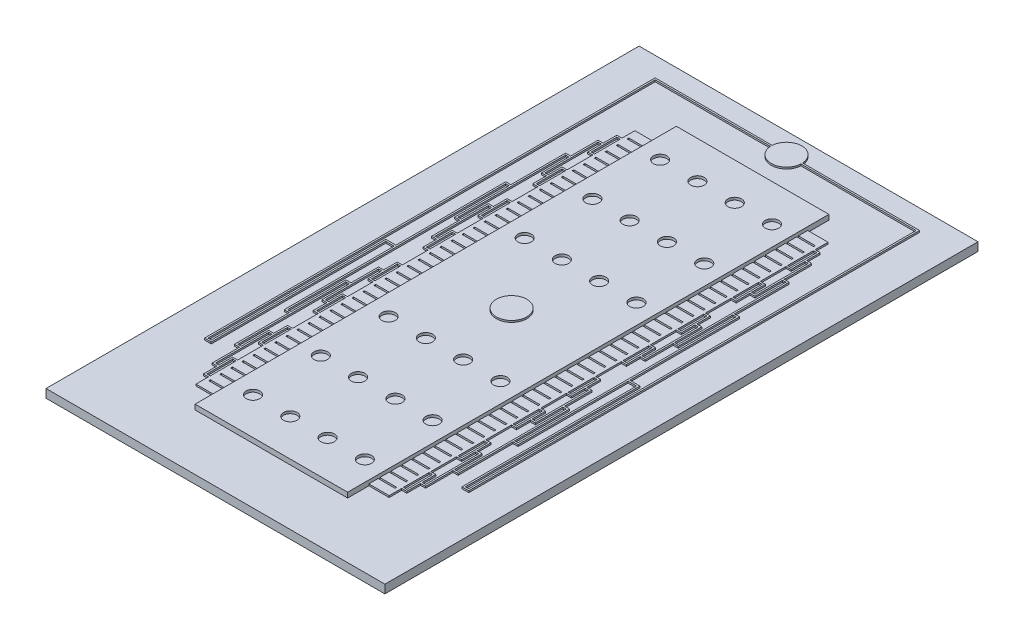
SolidWorks part; units mm, degrees
ref_plane "Front Plane" through (0, 0, 0) normal (0, 0, 1) x (1, 0, 0)
ref_plane "Top Plane" through (0, 0, 0) normal (0, 1, 0) x (1, 0, 0)
ref_plane "Right Plane" through (0, 0, 0) normal (1, 0, 0) x (0, 0, -1)
sketch "Sketch2" plane through (0, 0, 0) normal (0, 1, 0) x (1, 0, 0)
  line L1 (-10, 17.5) -> (10, 17.5)
  line L2 (-10, 17.5) -> (-10, -17.5)
  line L3 (-10, -17.5) -> (10, -17.5)
  line L4 (10, 17.5) -> (10, -17.5)
  line L5 (-10, 17.5) -> (10, -17.5) construction
  line L6 (-10, -17.5) -> (10, 17.5) construction
  point P0 (0, 0)
extrude "Boss-Extrude1" add sketch "Sketch2" along normal blind 0.5
sketch "Sketch3" plane through (0, 0.5, 0) normal (0, 1, 0) x (1, 0, 0)
  line L1 (-4.5, 14.2) -> (4.5, 14.2)
  line L2 (-4.5, 14.2) -> (-4.5, -14.2)
  line L3 (-4.5, -14.2) -> (4.5, -14.2)
  line L4 (4.5, 14.2) -> (4.5, -14.2)
  line L5 (-4.5, 14.2) -> (4.5, -14.2) construction
  line L6 (-4.5, -14.2) -> (4.5, 14.2) construction
  point P0 (0, 0)
extrude "Boss-Extrude2" add sketch "Sketch3" along normal blind 0.3
sketch "Sketch6" plane through (0, 0.5, 0) normal (0, 1, 0) x (1, 0, 0)
  line L0 (4.5, 12.95) -> (5.7, 12.95)
  line L1 (4.5, 12.95) -> (4.5, -12.95)
  line L2 (5.7, 12.95) -> (5.7, -12.95)
  line L3 (4.5, -12.95) -> (5.7, -12.95)
  line L4 (4.5, -14.2) -> (4.5, 14.2) construction
  line L5 (0, 23.9798) -> (0, -23.9798) construction
  line L6 (-5.7, 12.95) -> (-5.7, -12.95)
  line L7 (-4.5, -12.95) -> (-5.7, -12.95)
  line L8 (-4.5, 12.95) -> (-4.5, -12.95)
  line L9 (-4.5, 12.95) -> (-5.7, 12.95)
  point P0 (4.5, 14.1998)
  point P1 (4.5, 14.1998)
  point P6 (5.7, 0)
  point P10 (0, 0)
  point P14 (0, 0)
extrude "Boss-Extrude3" add sketch "Sketch6" along normal blind 0.1
sketch "Sketch8" plane through (0, 0.6, 0) normal (0, 1, 0) x (1, 0, 0)
  line L0 (4.5, 12.4) -> (5.5, 12.4)
  line L1 (4.5, 12.4) -> (4.5, 12.3)
  line L2 (5.5, 12.4) -> (5.5, 12.3)
  line L3 (4.5, 12.3) -> (5.5, 12.3)
  line L4 (-5.5, 12.4) -> (-4.5, 12.4)
  line L5 (-5.5, 12.4) -> (-5.5, 12.3)
  line L6 (-5.5, 12.3) -> (-4.5, 12.3)
  line L7 (-4.5, 12.4) -> (-4.5, 12.3)
  line L8 (-5.5, 11.75) -> (-4.5, 11.75)
  line L9 (-5.5, 11.75) -> (-5.5, 11.65)
  line L10 (-5.5, 11.65) -> (-4.5, 11.65)
  line L11 (-4.5, 11.75) -> (-4.5, 11.65)
  line L12 (-5.5, 11.1) -> (-4.5, 11.1)
  line L13 (-5.5, 11.1) -> (-5.5, 11)
  line L14 (-5.5, 11) -> (-4.5, 11)
  line L15 (-4.5, 11.1) -> (-4.5, 11)
  line L16 (-5.5, 10.45) -> (-4.5, 10.45)
  line L17 (-5.5, 10.45) -> (-5.5, 10.35)
  line L18 (-5.5, 10.35) -> (-4.5, 10.35)
  line L19 (-4.5, 10.45) -> (-4.5, 10.35)
  line L20 (-5.5, 9.8) -> (-4.5, 9.8)
  line L21 (-5.5, 9.8) -> (-5.5, 9.7)
  line L22 (-5.5, 9.7) -> (-4.5, 9.7)
  line L23 (-4.5, 9.8) -> (-4.5, 9.7)
  line L24 (-5.5, 9.15) -> (-4.5, 9.15)
  line L25 (-5.5, 9.15) -> (-5.5, 9.05)
  line L26 (-5.5, 9.05) -> (-4.5, 9.05)
  line L27 (-4.5, 9.15) -> (-4.5, 9.05)
  line L28 (-5.5, 8.5) -> (-4.5, 8.5)
  line L29 (-5.5, 8.5) -> (-5.5, 8.4)
  line L30 (-5.5, 8.4) -> (-4.5, 8.4)
  line L31 (-4.5, 8.5) -> (-4.5, 8.4)
  line L32 (-5.5, 7.85) -> (-4.5, 7.85)
  line L33 (-5.5, 7.85) -> (-5.5, 7.75)
  line L34 (-5.5, 7.75) -> (-4.5, 7.75)
  line L35 (-4.5, 7.85) -> (-4.5, 7.75)
  line L36 (-5.5, 7.2) -> (-4.5, 7.2)
  line L37 (-5.5, 7.2) -> (-5.5, 7.1)
  line L38 (-5.5, 7.1) -> (-4.5, 7.1)
  line L39 (-4.5, 7.2) -> (-4.5, 7.1)
  line L40 (-5.5, 6.55) -> (-4.5, 6.55)
  line L41 (-5.5, 6.55) -> (-5.5, 6.45)
  line L42 (-5.5, 6.45) -> (-4.5, 6.45)
  line L43 (-4.5, 6.55) -> (-4.5, 6.45)
  line L44 (-5.5, 5.9) -> (-4.5, 5.9)
  line L45 (-5.5, 5.9) -> (-5.5, 5.8)
  line L46 (-5.5, 5.8) -> (-4.5, 5.8)
  line L47 (-4.5, 5.9) -> (-4.5, 5.8)
  line L48 (-5.5, 5.25) -> (-4.5, 5.25)
  line L49 (-5.5, 5.25) -> (-5.5, 5.15)
  line L50 (-5.5, 5.15) -> (-4.5, 5.15)
  line L51 (-4.5, 5.25) -> (-4.5, 5.15)
  line L52 (-5.5, 4.6) -> (-4.5, 4.6)
  line L53 (-5.5, 4.6) -> (-5.5, 4.5)
  line L54 (-5.5, 4.5) -> (-4.5, 4.5)
  line L55 (-4.5, 4.6) -> (-4.5, 4.5)
  line L56 (-5.5, 3.95) -> (-4.5, 3.95)
  line L57 (-5.5, 3.95) -> (-5.5, 3.85)
  line L58 (-5.5, 3.85) -> (-4.5, 3.85)
  line L59 (-4.5, 3.95) -> (-4.5, 3.85)
  line L60 (-5.5, 3.3) -> (-4.5, 3.3)
  line L61 (-5.5, 3.3) -> (-5.5, 3.2)
  line L62 (-5.5, 3.2) -> (-4.5, 3.2)
  line L63 (-4.5, 3.3) -> (-4.5, 3.2)
  line L64 (-5.5, 2.65) -> (-4.5, 2.65)
  line L65 (-5.5, 2.65) -> (-5.5, 2.55)
  line L66 (-5.5, 2.55) -> (-4.5, 2.55)
  line L67 (-4.5, 2.65) -> (-4.5, 2.55)
  line L68 (-5.5, 2) -> (-4.5, 2)
  line L69 (-5.5, 2) -> (-5.5, 1.9)
  line L70 (-5.5, 1.9) -> (-4.5, 1.9)
  line L71 (-4.5, 2) -> (-4.5, 1.9)
  line L72 (-5.5, 1.35) -> (-4.5, 1.35)
  line L73 (-5.5, 1.35) -> (-5.5, 1.25)
  line L74 (-5.5, 1.25) -> (-4.5, 1.25)
  line L75 (-4.5, 1.35) -> (-4.5, 1.25)
  line L76 (-5.5, 0.7) -> (-4.5, 0.7)
  line L77 (-5.5, 0.7) -> (-5.5, 0.6)
  line L78 (-5.5, 0.6) -> (-4.5, 0.6)
  line L79 (-4.5, 0.7) -> (-4.5, 0.6)
  line L80 (-5.5, 0.05) -> (-4.5, 0.05)
  line L81 (-5.5, 0.05) -> (-5.5, -0.05)
  line L82 (-5.5, -0.05) -> (-4.5, -0.05)
  line L83 (-4.5, 0.05) -> (-4.5, -0.05)
  line L84 (-5.5, -0.6) -> (-4.5, -0.6)
  line L85 (-5.5, -0.6) -> (-5.5, -0.7)
  line L86 (-5.5, -0.7) -> (-4.5, -0.7)
  line L87 (-4.5, -0.6) -> (-4.5, -0.7)
  line L88 (-5.5, -1.25) -> (-4.5, -1.25)
  line L89 (-5.5, -1.25) -> (-5.5, -1.35)
  line L90 (-5.5, -1.35) -> (-4.5, -1.35)
  line L91 (-4.5, -1.25) -> (-4.5, -1.35)
  line L92 (-5.5, -1.9) -> (-4.5, -1.9)
  line L93 (-5.5, -1.9) -> (-5.5, -2)
  line L94 (-5.5, -2) -> (-4.5, -2)
  line L95 (-4.5, -1.9) -> (-4.5, -2)
  line L96 (-5.5, -2.55) -> (-4.5, -2.55)
  line L97 (-5.5, -2.55) -> (-5.5, -2.65)
  line L98 (-5.5, -2.65) -> (-4.5, -2.65)
  line L99 (-4.5, -2.55) -> (-4.5, -2.65)
  line L100 (-5.5, -3.2) -> (-4.5, -3.2)
  line L101 (-5.5, -3.2) -> (-5.5, -3.3)
  line L102 (-5.5, -3.3) -> (-4.5, -3.3)
  line L103 (-4.5, -3.2) -> (-4.5, -3.3)
  line L104 (-5.5, -3.85) -> (-4.5, -3.85)
  line L105 (-5.5, -3.85) -> (-5.5, -3.95)
  line L106 (-5.5, -3.95) -> (-4.5, -3.95)
  line L107 (-4.5, -3.85) -> (-4.5, -3.95)
  line L108 (-5.5, -4.5) -> (-4.5, -4.5)
  line L109 (-5.5, -4.5) -> (-5.5, -4.6)
  line L110 (-5.5, -4.6) -> (-4.5, -4.6)
  line L111 (-4.5, -4.5) -> (-4.5, -4.6)
  line L112 (-5.5, -5.15) -> (-4.5, -5.15)
  line L113 (-5.5, -5.15) -> (-5.5, -5.25)
  line L114 (-5.5, -5.25) -> (-4.5, -5.25)
  line L115 (-4.5, -5.15) -> (-4.5, -5.25)
  line L116 (-5.5, -5.8) -> (-4.5, -5.8)
  line L117 (-5.5, -5.8) -> (-5.5, -5.9)
  line L118 (-5.5, -5.9) -> (-4.5, -5.9)
  line L119 (-4.5, -5.8) -> (-4.5, -5.9)
  line L120 (-5.5, -6.45) -> (-4.5, -6.45)
  line L121 (-5.5, -6.45) -> (-5.5, -6.55)
  line L122 (-5.5, -6.55) -> (-4.5, -6.55)
  line L123 (-4.5, -6.45) -> (-4.5, -6.55)
  line L124 (-5.5, -7.1) -> (-4.5, -7.1)
  line L125 (-5.5, -7.1) -> (-5.5, -7.2)
  line L126 (-5.5, -7.2) -> (-4.5, -7.2)
  line L127 (-4.5, -7.1) -> (-4.5, -7.2)
  line L128 (-5.5, -7.75) -> (-4.5, -7.75)
  line L129 (-5.5, -7.75) -> (-5.5, -7.85)
  line L130 (-5.5, -7.85) -> (-4.5, -7.85)
  line L131 (-4.5, -7.75) -> (-4.5, -7.85)
  line L132 (-5.5, -8.4) -> (-4.5, -8.4)
  line L133 (-5.5, -8.4) -> (-5.5, -8.5)
  line L134 (-5.5, -8.5) -> (-4.5, -8.5)
  line L135 (-4.5, -8.4) -> (-4.5, -8.5)
  line L136 (-5.5, -9.05) -> (-4.5, -9.05)
  line L137 (-5.5, -9.05) -> (-5.5, -9.15)
  line L138 (-5.5, -9.15) -> (-4.5, -9.15)
  line L139 (-4.5, -9.05) -> (-4.5, -9.15)
  line L140 (-5.5, -9.7) -> (-4.5, -9.7)
  line L141 (-5.5, -9.7) -> (-5.5, -9.8)
  line L142 (-5.5, -9.8) -> (-4.5, -9.8)
  line L143 (-4.5, -9.7) -> (-4.5, -9.8)
  line L144 (-5.5, -10.35) -> (-4.5, -10.35)
  line L145 (-5.5, -10.35) -> (-5.5, -10.45)
  line L146 (-5.5, -10.45) -> (-4.5, -10.45)
  line L147 (-4.5, -10.35) -> (-4.5, -10.45)
  line L148 (-5.5, -11) -> (-4.5, -11)
  line L149 (-5.5, -11) -> (-5.5, -11.1)
  line L150 (-5.5, -11.1) -> (-4.5, -11.1)
  line L151 (-4.5, -11) -> (-4.5, -11.1)
  line L152 (-5.5, -11.65) -> (-4.5, -11.65)
  line L153 (-5.5, -11.65) -> (-5.5, -11.75)
  line L154 (-5.5, -11.75) -> (-4.5, -11.75)
  line L155 (-4.5, -11.65) -> (-4.5, -11.75)
  line L156 (-5.5, -12.3) -> (-4.5, -12.3)
  line L157 (-5.5, -12.3) -> (-5.5, -12.4)
  line L158 (-5.5, -12.4) -> (-4.5, -12.4)
  line L159 (-4.5, -12.3) -> (-4.5, -12.4)
  line L160 (4.5, 11.75) -> (5.5, 11.75)
  line L161 (4.5, 11.75) -> (4.5, 11.65)
  line L162 (4.5, 11.65) -> (5.5, 11.65)
  line L163 (5.5, 11.75) -> (5.5, 11.65)
  line L164 (4.5, 11.1) -> (5.5, 11.1)
  line L165 (4.5, 11.1) -> (4.5, 11)
  line L166 (4.5, 11) -> (5.5, 11)
  line L167 (5.5, 11.1) -> (5.5, 11)
  line L168 (4.5, 10.45) -> (5.5, 10.45)
  line L169 (4.5, 10.45) -> (4.5, 10.35)
  line L170 (4.5, 10.35) -> (5.5, 10.35)
  line L171 (5.5, 10.45) -> (5.5, 10.35)
  line L172 (4.5, 9.8) -> (5.5, 9.8)
  line L173 (4.5, 9.8) -> (4.5, 9.7)
  line L174 (4.5, 9.7) -> (5.5, 9.7)
  line L175 (5.5, 9.8) -> (5.5, 9.7)
  line L176 (4.5, 9.15) -> (5.5, 9.15)
  line L177 (4.5, 9.15) -> (4.5, 9.05)
  line L178 (4.5, 9.05) -> (5.5, 9.05)
  line L179 (5.5, 9.15) -> (5.5, 9.05)
  line L180 (4.5, 8.5) -> (5.5, 8.5)
  line L181 (4.5, 8.5) -> (4.5, 8.4)
  line L182 (4.5, 8.4) -> (5.5, 8.4)
  line L183 (5.5, 8.5) -> (5.5, 8.4)
  line L184 (4.5, 7.85) -> (5.5, 7.85)
  line L185 (4.5, 7.85) -> (4.5, 7.75)
  line L186 (4.5, 7.75) -> (5.5, 7.75)
  line L187 (5.5, 7.85) -> (5.5, 7.75)
  line L188 (4.5, 7.2) -> (5.5, 7.2)
  line L189 (4.5, 7.2) -> (4.5, 7.1)
  line L190 (4.5, 7.1) -> (5.5, 7.1)
  line L191 (5.5, 7.2) -> (5.5, 7.1)
  line L192 (4.5, 6.55) -> (5.5, 6.55)
  line L193 (4.5, 6.55) -> (4.5, 6.45)
  line L194 (4.5, 6.45) -> (5.5, 6.45)
  line L195 (5.5, 6.55) -> (5.5, 6.45)
  line L196 (4.5, 5.9) -> (5.5, 5.9)
  line L197 (4.5, 5.9) -> (4.5, 5.8)
  line L198 (4.5, 5.8) -> (5.5, 5.8)
  line L199 (5.5, 5.9) -> (5.5, 5.8)
  line L200 (4.5, 5.25) -> (5.5, 5.25)
  line L201 (4.5, 5.25) -> (4.5, 5.15)
  line L202 (4.5, 5.15) -> (5.5, 5.15)
  line L203 (5.5, 5.25) -> (5.5, 5.15)
  line L204 (4.5, 4.6) -> (5.5, 4.6)
  line L205 (4.5, 4.6) -> (4.5, 4.5)
  line L206 (4.5, 4.5) -> (5.5, 4.5)
  line L207 (5.5, 4.6) -> (5.5, 4.5)
  line L208 (4.5, 3.95) -> (5.5, 3.95)
  line L209 (4.5, 3.95) -> (4.5, 3.85)
  line L210 (4.5, 3.85) -> (5.5, 3.85)
  line L211 (5.5, 3.95) -> (5.5, 3.85)
  line L212 (4.5, 3.3) -> (5.5, 3.3)
  line L213 (4.5, 3.3) -> (4.5, 3.2)
  line L214 (4.5, 3.2) -> (5.5, 3.2)
  line L215 (5.5, 3.3) -> (5.5, 3.2)
  line L216 (4.5, 2.65) -> (5.5, 2.65)
  line L217 (4.5, 2.65) -> (4.5, 2.55)
  line L218 (4.5, 2.55) -> (5.5, 2.55)
  line L219 (5.5, 2.65) -> (5.5, 2.55)
  line L220 (4.5, 2) -> (5.5, 2)
  line L221 (4.5, 2) -> (4.5, 1.9)
  line L222 (4.5, 1.9) -> (5.5, 1.9)
  line L223 (5.5, 2) -> (5.5, 1.9)
  line L224 (4.5, 1.35) -> (5.5, 1.35)
  line L225 (4.5, 1.35) -> (4.5, 1.25)
  line L226 (4.5, 1.25) -> (5.5, 1.25)
  line L227 (5.5, 1.35) -> (5.5, 1.25)
  line L228 (4.5, 0.7) -> (5.5, 0.7)
  line L229 (4.5, 0.7) -> (4.5, 0.6)
  line L230 (4.5, 0.6) -> (5.5, 0.6)
  line L231 (5.5, 0.7) -> (5.5, 0.6)
  line L232 (4.5, 0.05) -> (5.5, 0.05)
  line L233 (4.5, 0.05) -> (4.5, -0.05)
  line L234 (4.5, -0.05) -> (5.5, -0.05)
  line L235 (5.5, 0.05) -> (5.5, -0.05)
  line L236 (4.5, -0.6) -> (5.5, -0.6)
  line L237 (4.5, -0.6) -> (4.5, -0.7)
  line L238 (4.5, -0.7) -> (5.5, -0.7)
  line L239 (5.5, -0.6) -> (5.5, -0.7)
  line L240 (4.5, -1.25) -> (5.5, -1.25)
  line L241 (4.5, -1.25) -> (4.5, -1.35)
  line L242 (4.5, -1.35) -> (5.5, -1.35)
  line L243 (5.5, -1.25) -> (5.5, -1.35)
  line L244 (4.5, -1.9) -> (5.5, -1.9)
  line L245 (4.5, -1.9) -> (4.5, -2)
  line L246 (4.5, -2) -> (5.5, -2)
  line L247 (5.5, -1.9) -> (5.5, -2)
  line L248 (4.5, -2.55) -> (5.5, -2.55)
  line L249 (4.5, -2.55) -> (4.5, -2.65)
  line L250 (4.5, -2.65) -> (5.5, -2.65)
  line L251 (5.5, -2.55) -> (5.5, -2.65)
  line L252 (4.5, -3.2) -> (5.5, -3.2)
  line L253 (4.5, -3.2) -> (4.5, -3.3)
  line L254 (4.5, -3.3) -> (5.5, -3.3)
  line L255 (5.5, -3.2) -> (5.5, -3.3)
  line L256 (4.5, -3.85) -> (5.5, -3.85)
  line L257 (4.5, -3.85) -> (4.5, -3.95)
  line L258 (4.5, -3.95) -> (5.5, -3.95)
  line L259 (5.5, -3.85) -> (5.5, -3.95)
  line L260 (4.5, -4.5) -> (5.5, -4.5)
  line L261 (4.5, -4.5) -> (4.5, -4.6)
  line L262 (4.5, -4.6) -> (5.5, -4.6)
  line L263 (5.5, -4.5) -> (5.5, -4.6)
  line L264 (4.5, -5.15) -> (5.5, -5.15)
  line L265 (4.5, -5.15) -> (4.5, -5.25)
  line L266 (4.5, -5.25) -> (5.5, -5.25)
  line L267 (5.5, -5.15) -> (5.5, -5.25)
  line L268 (4.5, -5.8) -> (5.5, -5.8)
  line L269 (4.5, -5.8) -> (4.5, -5.9)
  line L270 (4.5, -5.9) -> (5.5, -5.9)
  line L271 (5.5, -5.8) -> (5.5, -5.9)
  line L272 (4.5, -6.45) -> (5.5, -6.45)
  line L273 (4.5, -6.45) -> (4.5, -6.55)
  line L274 (4.5, -6.55) -> (5.5, -6.55)
  line L275 (5.5, -6.45) -> (5.5, -6.55)
  line L276 (4.5, -7.1) -> (5.5, -7.1)
  line L277 (4.5, -7.1) -> (4.5, -7.2)
  line L278 (4.5, -7.2) -> (5.5, -7.2)
  line L279 (5.5, -7.1) -> (5.5, -7.2)
  line L280 (4.5, -7.75) -> (5.5, -7.75)
  line L281 (4.5, -7.75) -> (4.5, -7.85)
  line L282 (4.5, -7.85) -> (5.5, -7.85)
  line L283 (5.5, -7.75) -> (5.5, -7.85)
  line L284 (4.5, -8.4) -> (5.5, -8.4)
  line L285 (4.5, -8.4) -> (4.5, -8.5)
  line L286 (4.5, -8.5) -> (5.5, -8.5)
  line L287 (5.5, -8.4) -> (5.5, -8.5)
  line L288 (4.5, -9.05) -> (5.5, -9.05)
  line L289 (4.5, -9.05) -> (4.5, -9.15)
  line L290 (4.5, -9.15) -> (5.5, -9.15)
  line L291 (5.5, -9.05) -> (5.5, -9.15)
  line L292 (4.5, -9.7) -> (5.5, -9.7)
  line L293 (4.5, -9.7) -> (4.5, -9.8)
  line L294 (4.5, -9.8) -> (5.5, -9.8)
  line L295 (5.5, -9.7) -> (5.5, -9.8)
  line L296 (4.5, -10.35) -> (5.5, -10.35)
  line L297 (4.5, -10.35) -> (4.5, -10.45)
  line L298 (4.5, -10.45) -> (5.5, -10.45)
  line L299 (5.5, -10.35) -> (5.5, -10.45)
  line L300 (4.5, -11) -> (5.5, -11)
  line L301 (4.5, -11) -> (4.5, -11.1)
  line L302 (4.5, -11.1) -> (5.5, -11.1)
  line L303 (5.5, -11) -> (5.5, -11.1)
  line L304 (4.5, -11.65) -> (5.5, -11.65)
  line L305 (4.5, -11.65) -> (4.5, -11.75)
  line L306 (4.5, -11.75) -> (5.5, -11.75)
  line L307 (5.5, -11.65) -> (5.5, -11.75)
  line L308 (4.5, -12.3) -> (5.5, -12.3)
  line L309 (4.5, -12.3) -> (4.5, -12.4)
  line L310 (4.5, -12.4) -> (5.5, -12.4)
  line L311 (5.5, -12.3) -> (5.5, -12.4)
  point P0 (4.5, 12.4)
  dimension "D1" = 0.55
  dimension "D2" = 2
  dimension "D3" = 39
extrude "Cut-Extrude1" cut sketch "Sketch8" against normal blind 0.1 contours L0 L1 L3 L2 | L162 L163 L160 L161 | L166 L167 L164 L165 | L170 L171 L168 L169 | L174 L175 L172 L173 | L176 L179 L178 L177 | L182 L183 L180 L181 | L184 L187 L186 L185 | L188 L191 L190 L189 | L192 L195 L194 L193 | L196 L199 L198 L197 | L200 L203 L202 L201 | L204 L207 L206 L205 | L208 L211 L210 L209 | L212 L215 L214 L213 | L216 L219 L218 L217 | L220 L223 L222 L221 | L224 L227 L226 L225 | L228 L231 L230 L229 | L232 L235 L234 L233 | L236 L239 L238 L237 | L240 L243 L242 L241 | L244 L247 L246 L245 | L248 L251 L250 L249 | L254 L255 L252 L253 | L256 L259 L258 L257 | L260 L263 L262 L261 | L266 L267 L264 L265 | L268 L271 L270 L269 | L272 L275 L274 L273 | L276 L279 L278 L277 | L280 L283 L282 L281 | L284 L287 L286 L285 | L288 L291 L290 L289 | L292 L295 L294 L293 | L296 L299 L298 L297 | L300 L303 L302 L301 | L304 L307 L306 L305 | L308 L311 L310 L309 | L156 L159 L158 L157 | L152 L155 L154 L153 | L150 L151 L148 L149 | L144 L147 L146 L145 | L140 L143 L142 L141 | L136 L139 L138 L137 | L134 L135 L132 L133 | L128 L131 L130 L129 | L124 L127 L126 L125 | L120 L123 L122 L121 | L116 L119 L118 L117 | L112 L115 L114 L113 | L108 L111 L110 L109 | L104 L107 L106 L105 | L100 L103 L102 L101 | L98 L99 L96 L97 | L94 L95 L92 L93 | L4 L7 L6 L5 | L8 L11 L10 L9 | L12 L15 L14 L13 | L16 L19 L18 L17 | L20 L23 L22 L21 | L24 L27 L26 L25 | L28 L31 L30 L29 | L32 L35 L34 L33 | L36 L39 L38 L37 | L40 L43 L42 L41 | L44 L47 L46 L45 | L48 L51 L50 L49 | L52 L55 L54 L53 | L56 L59 L58 L57 | L88 L91 L90 L89 | L84 L87 L86 L85 | L82 L83 L80 L81 | L78 L79 L76 L77 | L72 L75 L74 L73 | L68 L71 L70 L69 | L64 L67 L66 L65 | L60 L63 L62 L61
sketch "Sketch9" plane through (0, 0.5, 0) normal (0, 1, 0) x (1, 0, 0)
  line L0 (0, 23.039) -> (0, -23.039) construction
  line L1 (-7.8, 16.25) -> (7.8, 16.25)
  line L2 (4.5, 14.2) -> (-4.5, 14.2) construction
  line L3 (-7.7, 16.15) -> (7.7, 16.15)
  line L4 (-7.8, 16.25) -> (-7.8, -10.35)
  line L5 (-7.7, 16.15) -> (-7.7, -10.25)
  line L6 (-7.8, -10.35) -> (-7.4, -10.35)
  line L7 (-7.7, -10.25) -> (-7.5, -10.25)
  line L8 (8.7438, 0) -> (-8.7438, 0) construction
  line L9 (-7.5, -10.25) -> (-7.5, 0.05)
  line L10 (-7.4, -10.35) -> (-7.4, -0.05)
  line L11 (-5.7, 12.95) -> (-5.7, -12.95) construction
  line L12 (-7.5, 0.05) -> (-6.9, 0.05)
  line L13 (-7.4, -0.05) -> (-6.9, -0.05)
  line L14 (-5.7, 12.19) -> (-6, 12.19)
  line L15 (-5.7, 12.09) -> (-5.9, 12.09)
  line L16 (-5.7, 10.57) -> (-5.9, 10.57)
  line L17 (-5.7, 10.47) -> (-6, 10.47)
  line L18 (-5.9, 12.09) -> (-5.9, 10.57)
  line L19 (-6, 12.19) -> (-6, 11.38)
  line L20 (-6, 10.47) -> (-6, 11.28)
  line L21 (-6, 8.95) -> (-6, 8.14)
  line L22 (-5.9, 8.85) -> (-5.9, 7.33)
  line L23 (-6, 7.23) -> (-6, 8.04)
  line L24 (-5.7, 7.33) -> (-5.9, 7.33)
  line L25 (-5.7, 7.23) -> (-6, 7.23)
  line L26 (-5.7, 8.95) -> (-6, 8.95)
  line L27 (-5.7, 8.85) -> (-5.9, 8.85)
  line L28 (-6, 5.71) -> (-6, 4.9)
  line L29 (-5.9, 5.61) -> (-5.9, 4.09)
  line L30 (-6, 3.99) -> (-6, 4.8)
  line L31 (-5.7, 4.09) -> (-5.9, 4.09)
  line L32 (-5.7, 3.99) -> (-6, 3.99)
  line L33 (-5.7, 5.71) -> (-6, 5.71)
  line L34 (-5.7, 5.61) -> (-5.9, 5.61)
  line L35 (-6, 2.47) -> (-6, 1.66)
  line L36 (-5.9, 2.37) -> (-5.9, 0.85)
  line L37 (-6, 0.75) -> (-6, 1.56)
  line L38 (-5.7, 0.85) -> (-5.9, 0.85)
  line L39 (-5.7, 0.75) -> (-6, 0.75)
  line L40 (-5.7, 2.47) -> (-6, 2.47)
  line L41 (-5.7, 2.37) -> (-5.9, 2.37)
  line L42 (-6, -0.77) -> (-6, -1.58)
  line L43 (-5.9, -0.87) -> (-5.9, -2.39)
  line L44 (-6, -2.49) -> (-6, -1.68)
  line L45 (-5.7, -2.39) -> (-5.9, -2.39)
  line L46 (-5.7, -2.49) -> (-6, -2.49)
  line L47 (-5.7, -0.77) -> (-6, -0.77)
  line L48 (-5.7, -0.87) -> (-5.9, -0.87)
  line L49 (-6, -4.01) -> (-6, -4.82)
  line L50 (-5.9, -4.11) -> (-5.9, -5.63)
  line L51 (-6, -5.73) -> (-6, -4.92)
  line L52 (-5.7, -5.63) -> (-5.9, -5.63)
  line L53 (-5.7, -5.73) -> (-6, -5.73)
  line L54 (-5.7, -4.01) -> (-6, -4.01)
  line L55 (-5.7, -4.11) -> (-5.9, -4.11)
  line L56 (-6, -7.25) -> (-6, -8.06)
  line L57 (-5.9, -7.35) -> (-5.9, -8.87)
  line L58 (-6, -8.97) -> (-6, -8.16)
  line L59 (-5.7, -8.87) -> (-5.9, -8.87)
  line L60 (-5.7, -8.97) -> (-6, -8.97)
  line L61 (-5.7, -7.25) -> (-6, -7.25)
  line L62 (-5.7, -7.35) -> (-5.9, -7.35)
  line L63 (-6, -10.49) -> (-6, -11.3)
  line L64 (-5.9, -10.59) -> (-5.9, -12.11)
  line L65 (-6, -12.21) -> (-6, -11.4)
  line L66 (-5.7, -12.11) -> (-5.9, -12.11)
  line L67 (-5.7, -12.21) -> (-6, -12.21)
  line L68 (-5.7, -10.49) -> (-6, -10.49)
  line L69 (-5.7, -10.59) -> (-5.9, -10.59)
  line L70 (-6, 11.38) -> (-6.3, 11.38)
  line L71 (-6, 11.28) -> (-6.2, 11.28)
  line L72 (-6, 8.14) -> (-6.2, 8.14)
  line L73 (-6, 8.04) -> (-6.3, 8.04)
  line L74 (-6, 4.9) -> (-6.3, 4.9)
  line L75 (-6, 4.8) -> (-6.2, 4.8)
  line L76 (-6, 1.56) -> (-6.3, 1.56)
  line L77 (-6, 1.66) -> (-6.2, 1.66)
  line L78 (-6, -1.58) -> (-6.3, -1.58)
  line L79 (-6, -1.68) -> (-6.2, -1.68)
  line L80 (-6, -4.92) -> (-6.3, -4.92)
  line L81 (-6, -4.82) -> (-6.2, -4.82)
  line L82 (-6, -8.06) -> (-6.3, -8.06)
  line L83 (-6, -8.16) -> (-6.2, -8.16)
  line L84 (-6, -11.4) -> (-6.3, -11.4)
  line L85 (-6, -11.3) -> (-6.2, -11.3)
  line L86 (-6.2, -8.16) -> (-6.2, -11.3)
  line L87 (-6.2, -1.68) -> (-6.2, -4.82)
  line L88 (-6.2, 4.8) -> (-6.2, 1.66)
  line L89 (-6.2, 11.28) -> (-6.2, 8.14)
  line L90 (-6.3, 11.38) -> (-6.3, 9.76)
  line L91 (-6.3, 8.04) -> (-6.3, 9.66)
  line L92 (-6.3, 4.9) -> (-6.3, 3.2981)
  line L93 (-6.3, 1.56) -> (-6.3, 3.2104)
  line L94 (-6.3, -1.58) -> (-6.3, -3.2)
  line L95 (-6.3, -4.92) -> (-6.3, -3.3)
  line L96 (-6.3, -8.06) -> (-6.3, -9.68)
  line L97 (-6.3, -11.4) -> (-6.3, -9.78)
  line L98 (-6.3, -9.78) -> (-6.6, -9.78)
  line L99 (-6.3, -9.68) -> (-6.5, -9.68)
  line L100 (-6.3, -3.2) -> (-6.6, -3.2)
  line L101 (-6.3, -3.3) -> (-6.5, -3.3)
  line L102 (-6.3, 3.2104) -> (-6.6, 3.2104)
  line L103 (-6.3, 3.2981) -> (-6.5, 3.2981)
  line L104 (-6.3, 9.76) -> (-6.6, 9.76)
  line L105 (-6.3, 9.66) -> (-6.5, 9.66)
  line L106 (-6.5, -9.68) -> (-6.5, -3.3)
  line L107 (-6.5, 3.2981) -> (-6.5, 9.66)
  line L108 (-6.6, 9.76) -> (-6.6, 6.529)
  line L109 (-6.6, 3.2104) -> (-6.6, 6.429)
  line L110 (-6.6, -3.2) -> (-6.6, -6.44)
  line L111 (-6.6, -9.78) -> (-6.6, -6.54)
  line L112 (-6.6, -6.54) -> (-6.9, -6.54)
  line L113 (-6.6, -6.44) -> (-6.8, -6.44)
  line L114 (-6.6, 6.529) -> (-6.9, 6.529)
  line L115 (-6.6, 6.429) -> (-6.8, 6.429)
  line L116 (-6.9, -6.54) -> (-6.9, -0.05)
  line L117 (-6.9, 6.529) -> (-6.9, 0.05)
  line L118 (-6.8, -6.44) -> (-6.8, 6.429)
  line L119 (5.7, -12.21) -> (6, -12.21)
  line L120 (5.7, -12.11) -> (5.9, -12.11)
  line L121 (6, -12.21) -> (6, -11.4)
  line L122 (6, -11.4) -> (6.3, -11.4)
  line L123 (6, -11.3) -> (6.2, -11.3)
  line L124 (5.9, -10.59) -> (5.9, -12.11)
  line L125 (6, -10.49) -> (6, -11.3)
  line L126 (5.7, -10.59) -> (5.9, -10.59)
  line L127 (5.7, -10.49) -> (6, -10.49)
  line L128 (6.3, -9.68) -> (6.5, -9.68)
  line L129 (6.3, -11.4) -> (6.3, -9.78)
  line L130 (6.3, -9.78) -> (6.6, -9.78)
  line L131 (7.8, -10.35) -> (7.4, -10.35)
  line L132 (7.7, -10.25) -> (7.5, -10.25)
  line L133 (5.7, -8.97) -> (6, -8.97)
  line L134 (5.7, -8.87) -> (5.9, -8.87)
  line L135 (6, -8.97) -> (6, -8.16)
  line L136 (6.3, -8.06) -> (6.3, -9.68)
  line L137 (6.2, -8.16) -> (6.2, -11.3)
  line L138 (6, -8.16) -> (6.2, -8.16)
  line L139 (6, -8.06) -> (6.3, -8.06)
  line L140 (5.9, -7.35) -> (5.9, -8.87)
  line L141 (6, -7.25) -> (6, -8.06)
  line L142 (5.7, -7.35) -> (5.9, -7.35)
  line L143 (5.7, -7.25) -> (6, -7.25)
  line L144 (6.6, -9.78) -> (6.6, -6.54)
  line L145 (6.6, -6.54) -> (6.9, -6.54)
  line L146 (6.6, -6.44) -> (6.8, -6.44)
  line L147 (5.7, -5.73) -> (6, -5.73)
  line L148 (5.7, -5.63) -> (5.9, -5.63)
  line L149 (6, -5.73) -> (6, -4.92)
  line L150 (5.9, -4.11) -> (5.9, -5.63)
  line L151 (5.7, -4.01) -> (6, -4.01)
  line L152 (5.7, -4.11) -> (5.9, -4.11)
  line L153 (6, -4.01) -> (6, -4.82)
  line L154 (6, -4.92) -> (6.3, -4.92)
  line L155 (6, -4.82) -> (6.2, -4.82)
  line L156 (6.3, -4.92) -> (6.3, -3.3)
  line L157 (6.6, -3.2) -> (6.6, -6.44)
  line L158 (6.5, -9.68) -> (6.5, -3.3)
  line L159 (6.3, -3.3) -> (6.5, -3.3)
  line L160 (6.3, -3.2) -> (6.6, -3.2)
  line L161 (5.7, -2.49) -> (6, -2.49)
  line L162 (5.7, -2.39) -> (5.9, -2.39)
  line L163 (6, -2.49) -> (6, -1.68)
  line L164 (6.3, -1.58) -> (6.3, -3.2)
  line L165 (6.2, -1.68) -> (6.2, -4.82)
  line L166 (6, -1.68) -> (6.2, -1.68)
  line L167 (6, -1.58) -> (6.3, -1.58)
  line L168 (5.9, -0.87) -> (5.9, -2.39)
  line L169 (6, -0.77) -> (6, -1.58)
  line L170 (5.7, -0.87) -> (5.9, -0.87)
  line L171 (5.7, -0.77) -> (6, -0.77)
  line L172 (6.9, -6.54) -> (6.9, -0.05)
  line L173 (7.5, -10.25) -> (7.5, 0.05)
  line L174 (7.4, -10.35) -> (7.4, -0.05)
  line L175 (7.4, -0.05) -> (6.9, -0.05)
  line L176 (7.5, 0.05) -> (6.9, 0.05)
  line L177 (5.7, 0.75) -> (6, 0.75)
  line L178 (5.7, 0.85) -> (5.9, 0.85)
  line L179 (6, 0.75) -> (6, 1.56)
  line L180 (6, 1.56) -> (6.3, 1.56)
  line L181 (6, 1.66) -> (6.2, 1.66)
  line L182 (5.9, 2.37) -> (5.9, 0.85)
  line L183 (6, 2.47) -> (6, 1.66)
  line L184 (5.7, 2.37) -> (5.9, 2.37)
  line L185 (5.7, 2.47) -> (6, 2.47)
  line L186 (6.3, 3.2104) -> (6.6, 3.2104)
  line L187 (6.3, 1.56) -> (6.3, 3.2104)
  line L188 (6.3, 3.2981) -> (6.5, 3.2981)
  line L189 (5.7, 3.99) -> (6, 3.99)
  line L190 (5.7, 4.09) -> (5.9, 4.09)
  line L191 (6.3, 4.9) -> (6.3, 3.2981)
  line L192 (6.2, 4.8) -> (6.2, 1.66)
  line L193 (6, 3.99) -> (6, 4.8)
  line L194 (6, 4.8) -> (6.2, 4.8)
  line L195 (6, 4.9) -> (6.3, 4.9)
  line L196 (6, 5.71) -> (6, 4.9)
  line L197 (5.9, 5.61) -> (5.9, 4.09)
  line L198 (5.7, 5.61) -> (5.9, 5.61)
  line L199 (5.7, 5.71) -> (6, 5.71)
  line L200 (6.6, 3.2104) -> (6.6, 6.429)
  line L201 (6.9, 6.529) -> (6.9, 0.05)
  line L202 (6.8, -6.44) -> (6.8, 6.429)
  line L203 (6.6, 6.429) -> (6.8, 6.429)
  line L204 (6.6, 6.529) -> (6.9, 6.529)
  line L205 (5.7, 7.23) -> (6, 7.23)
  line L206 (5.7, 7.33) -> (5.9, 7.33)
  line L207 (6, 7.23) -> (6, 8.04)
  line L208 (6, 8.04) -> (6.3, 8.04)
  line L209 (6, 8.14) -> (6.2, 8.14)
  line L210 (5.9, 8.85) -> (5.9, 7.33)
  line L211 (6, 8.95) -> (6, 8.14)
  line L212 (5.7, 8.85) -> (5.9, 8.85)
  line L213 (5.7, 8.95) -> (6, 8.95)
  line L214 (6.3, 8.04) -> (6.3, 9.66)
  line L215 (6.6, 9.76) -> (6.6, 6.529)
  line L216 (6.5, 3.2981) -> (6.5, 9.66)
  line L217 (6.3, 9.66) -> (6.5, 9.66)
  line L218 (6.3, 9.76) -> (6.6, 9.76)
  line L219 (6.2, 11.28) -> (6.2, 8.14)
  line L220 (6.3, 11.38) -> (6.3, 9.76)
  line L221 (5.7, 10.47) -> (6, 10.47)
  line L222 (5.7, 10.57) -> (5.9, 10.57)
  line L223 (6, 10.47) -> (6, 11.28)
  line L224 (6, 11.28) -> (6.2, 11.28)
  line L225 (6, 11.38) -> (6.3, 11.38)
  line L226 (5.9, 12.09) -> (5.9, 10.57)
  line L227 (6, 12.19) -> (6, 11.38)
  line L228 (5.7, 12.09) -> (5.9, 12.09)
  line L229 (5.7, 12.19) -> (6, 12.19)
  line L230 (7.7, 16.15) -> (7.7, -10.25)
  line L231 (7.8, 16.25) -> (7.8, -10.35)
  circle A0 centre (0, 16.2) radius 0.9
  point P0 (0, 0)
  point P1 (0, 16.15)
  point P5 (0, 0)
  point P6 (0, 16.2)
  point P9 (0, 14.2)
  point P12 (0, 16.25)
  point P18 (0, 16.25)
  point P20 (0, 16.15)
  point P22 (-7.5, 0)
  point P26 (0, 0)
  point P30 (-5.7, 0)
  point P33 (-5.7, 12.19)
  point P34 (-5.7, 12.95)
  point P38 (-5.7, 12.14)
  point P39 (-5.7, 11.33)
  point P40 (-5.7, 10.52)
  point P41 (-5.7, 9.71)
  point P42 (-5.7, 8.9)
  point P43 (-5.7, 8.09)
  point P44 (-5.7, 7.28)
  point P45 (-5.7, 6.47)
  point P46 (-5.7, 5.66)
  point P47 (-5.7, 4.85)
  point P48 (-5.7, 4.04)
  point P49 (-5.7, 3.23)
  point P50 (-5.7, 2.42)
  point P51 (-5.7, 1.61)
  point P52 (-5.7, 0.8)
  point P53 (-5.7, -0.01)
  point P54 (-5.7, -0.82)
  point P55 (-5.7, -1.63)
  point P56 (-5.7, -2.44)
  point P57 (-5.7, -3.25)
  point P58 (-5.7, -4.06)
  point P59 (-5.7, -4.87)
  point P60 (-5.7, -5.68)
  point P61 (-5.7, -6.49)
  point P62 (-5.7, -7.3)
  point P63 (-5.7, -8.11)
  point P64 (-5.7, -8.92)
  point P65 (-5.7, -9.73)
  point P66 (-5.7, -10.54)
  point P67 (-5.7, -11.35)
  point P68 (-5.7, -12.16)
  point P69 (-5.7, -12.97)
  point P70 (-5.7, 12.09)
  point P71 (-5.7, 10.47)
  point P72 (-5.7, 10.57)
  point P73 (-5.7, 8.95)
  point P74 (-5.7, 8.85)
  point P75 (-5.7, 7.33)
  point P76 (-5.7, 7.23)
  point P77 (-5.7, 5.71)
  point P78 (-5.7, 5.61)
  point P79 (-5.7, 4.09)
  point P80 (-5.7, 3.99)
  point P81 (-5.7, 2.47)
  point P82 (-5.7, 2.37)
  point P83 (-5.7, 0.85)
  point P84 (-5.7, 0.75)
  point P87 (-5.9, 11.28)
  point P94 (-5.9, 11.33)
  point P96 (-5.9, 11.38)
  point P179 (-6.2, 3.18)
  point P180 (-6.2, 9.76)
  point P182 (-6.2, 9.66)
  point P183 (-6.2, -3.2)
  point P184 (-6.2, -3.3)
  point P186 (-6.2, -9.68)
  point P187 (-6.2, -9.78)
  point P188 (-6.2, 3.28)
  point P192 (-6.2, 3.23)
  point P198 (-6.2, 9.71)
  point P203 (-6.2, -3.25)
  point P206 (-6.2, -9.73)
  point P208 (-6.5, -6.54)
  point P211 (-6.5, -6.44)
  point P212 (-6.5, 6.529)
  point P214 (-6.5, 6.429)
  point P220 (-6.5, -6.49)
  point P221 (-6.5, 6.479)
  line M13 (-5.7, -12.95) -> (-5.7, 12.95)
  line M19 (5.7, 12.95) -> (5.7, -12.95)
  dimension "D2" = 0.05
  dimension "D1" = 2
  dimension "D3" = 0.05
  dimension "D4" = 0.05
  dimension "D5" = 0.05
  dimension "D6" = 33
  dimension "D7" = 0.05
  dimension "D8" = 0.05
  dimension "D9" = 0.05
  dimension "D10" = 0.05
  dimension "D11" = 0.05
  dimension "D12" = 0.05
  dimension "D13" = 0.05
  dimension "D14" = 0.05
  dimension "D15" = 0.05
  dimension "D16" = 0.05
  dimension "D17" = 0.05
  dimension "D18" = 0.05
  dimension "D19" = 0.05
  dimension "D20" = 0.05
  dimension "D21" = 0.05
  dimension "D22" = 0.05
  dimension "D23" = 0.05
  dimension "D24" = 0.05
  dimension "D25" = 8
  dimension "D26" = 0.05
  dimension "D27" = 0.05
  dimension "D28" = 0.05
  dimension "D29" = 0.05
  dimension "D30" = 0.05
  dimension "D31" = 0.05
  dimension "D32" = 0.05
  dimension "D33" = 0.05
  dimension "D34" = 0.05
  dimension "D35" = 0.05
  dimension "D36" = 0.05
  dimension "D37" = 0.05
  dimension "D38" = 0.1
  dimension "D39" = 0.2
  dimension "D40" = 0.3
  dimension "D41" = 0.1
  dimension "D42" = 0.3
  dimension "D43" = 0.2
  dimension "D44" = 0.2
  dimension "D45" = 0.3
  dimension "D46" = 0.2
  dimension "D47" = 0.3
  dimension "D48" = 0.1
  dimension "D49" = 0.2
  dimension "D50" = 0.3
  dimension "D51" = 0.1
  dimension "D52" = 0.1
  dimension "D53" = 0.1
  dimension "D54" = 0.1
  dimension "D55" = 0.3
  dimension "D56" = 0.2
  dimension "D57" = 0.3
  dimension "0.1" = 0.1
  dimension "D58" = 0.2
  dimension "D59" = 0.1
  dimension "D60" = 0.2
  dimension "0.3" = 0.3
  dimension "D61" = 0.1
  dimension "D62" = 0.2
  dimension "D63" = 0.3
  dimension "D64" = 0.3
  dimension "D65" = 0.2
  dimension "D66" = 0.1
  dimension "D67" = 0.5
extrude "Boss-Extrude4" add sketch "Sketch9" along normal blind 0.1 contours A0 L1 L4 L6 L10 L13 L116 L112 L111 L98 L97 L84 L65 L67 L66 L64 L69 L68 L63 L85 L86 L83 L58 L60 L59 L57 L62 L61 L56 L82 L96 L99 L106 L101 L95 L80 L51 L53 L52 L50 L55 L54 L49 L81 L87 M13 | A0 L3 L230 L132 L173 L176 L201 L204 L215 L218 L220 L225 L227 L229 L228 L226 L222 L221 L223 L224 L219 L209 L211 L213 L212 L210 L206 L205 L207 L208 L214 L217 L216 L188 L191 L195 L196 L199 L198 L197 L190 L189 L193 L194 L192 M19 | L3 A0 L1 | L1 A0 | L3 A0 region at (-4.3493, 0.5, -16.2207) region at (0, 0.5, -16.6091) region at (0, 0.5, -16.2) region at (4.3493, 0.5, -16.2207) region at (0, 0.5, -15.7909)
sketch "Sketch10" plane through (0, 0.8, 0) normal (0, 1, 0) x (1, 0, 0)
  line L0 (-4.2645, 0) -> (4.2645, 0) construction
  line L1 (0, -14.0113) -> (0, 14.0113) construction
  circle A1 centre (0.025, -0.0492) radius 0.9
  point P3 (0, 0)
  point P6 (0, 0)
extrude "Boss-Extrude5" add sketch "Sketch10" along normal blind 0.1 contours A1
sketch "Sketch11" plane through (0, 0.8, 0) normal (0, 1, 0) x (1, 0, 0)
  line L1 (-4.1511, 0) -> (4.1511, 0) construction
  line L2 (0, -13.9488) -> (0, 13.9488) construction
  circle A0 centre (-3.2696, 12.0132) radius 0.4
  circle A1 centre (-1.0696, 12.0132) radius 0.4
  circle A2 centre (1.1304, 12.0132) radius 0.4
  circle A3 centre (3.3304, 12.0132) radius 0.4
  circle A4 centre (-1.0696, 8.0132) radius 0.4
  circle A5 centre (1.1304, 8.0132) radius 0.4
  circle A6 centre (3.3304, 8.0132) radius 0.4
  circle A7 centre (-1.0696, 4.0132) radius 0.4
  circle A8 centre (1.1304, 4.0132) radius 0.4
  circle A9 centre (3.3304, 4.0132) radius 0.4
  circle A10 centre (-3.2696, 8.0132) radius 0.4
  circle A11 centre (-3.2696, 4.0132) radius 0.4
  circle A12 centre (3.3304, -4.0132) radius 0.4
  circle A13 centre (1.1304, -4.0132) radius 0.4
  circle A14 centre (-1.0696, -4.0132) radius 0.4
  circle A15 centre (-3.2696, -4.0132) radius 0.4
  circle A16 centre (3.3304, -8.0132) radius 0.4
  circle A17 centre (1.1304, -8.0132) radius 0.4
  circle A18 centre (-1.0696, -8.0132) radius 0.4
  circle A19 centre (-3.2696, -8.0132) radius 0.4
  circle A20 centre (3.3304, -12.0132) radius 0.4
  circle A21 centre (1.1304, -12.0132) radius 0.4
  circle A22 centre (-1.0696, -12.0132) radius 0.4
  circle A23 centre (-3.2696, -12.0132) radius 0.4
  point P5 (0, 0)
  point P8 (0, 0)
  dimension "D1" = 4
  dimension "D2" = 3
extrude "Cut-Extrude2" cut sketch "Sketch11" against normal blind 0.15
